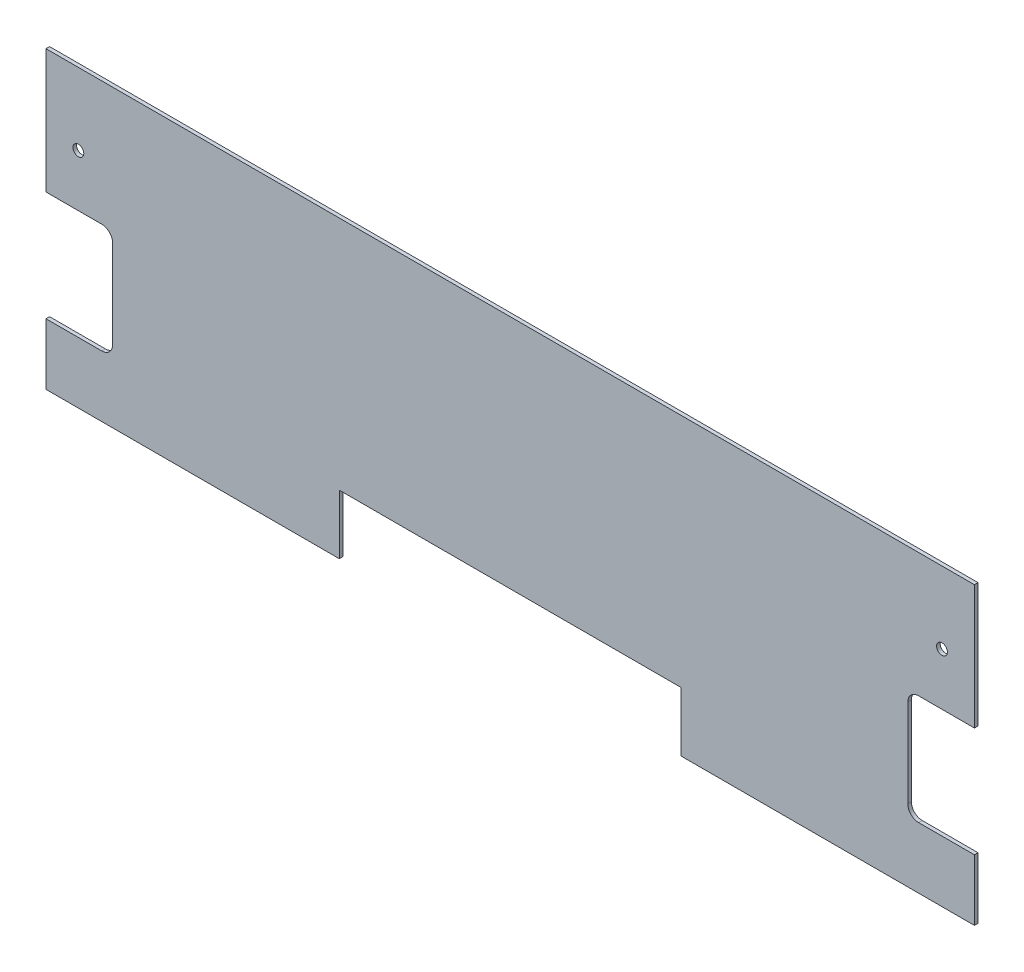
SolidWorks part; units mm, degrees
material "Film PE haute densité"
ref_plane "Front" through (0, 0, 0) normal (0, 0, 1) x (1, 0, 0)
ref_plane "Top" through (0, 0, 0) normal (0, 1, 0) x (1, 0, 0)
ref_plane "Right" through (0, 0, 0) normal (1, 0, 0) x (0, 0, -1)
sketch "Esquisse1" plane through (0, 0, 0) normal (0, 0, 1) x (1, 0, 0)
  line L0 (47.5, -82) -> (129, -82)
  line L1 (-129, -82) -> (-47.5, -82)
  line L2 (-129, -82) -> (-129, 0)
  line L3 (-129, 0) -> (129, 0)
  line L4 (129, -82) -> (129, 0)
  line L6 (-47.5, -82) -> (-47.5, -65.5)
  line L7 (-47.5, -65.5) -> (47.5, -65.5)
  line L8 (47.5, -82) -> (47.5, -65.5)
  dimension "D1" = 82
  dimension "D2" = 16.5
  dimension "D3" = 95
  dimension "D4" = 258
base flange "Tôle de base pliée1" sketch "Esquisse1" thickness 1 reverse thickness direction no parameters "D1"=1.5
sketch "Esquisse6" plane through (0, 0, 0) normal (0, 0, 1) x (1, 0, 0)
  line L0 (-129, 0) -> (-129, -82) construction
  line L1 (-129, -34.5) -> (-110.5, -34.5)
  line L2 (-129, -34.5) -> (-129, -65)
  line L3 (-129, -65) -> (-110.5, -65)
  line L4 (-110.5, -34.5) -> (-110.5, -65)
  line L5 (0, -50) -> (0, 50) construction
  line L6 (129, -65) -> (110.5, -65)
  line L7 (110.5, -34.5) -> (110.5, -65)
  line L8 (129, -34.5) -> (110.5, -34.5)
  line L9 (129, -34.5) -> (129, -65)
  line L10 (-129, -82) -> (-47.5, -82) construction
  line L11 (129, 0) -> (-129, 0) construction
  circle A0 centre (-120, -20) radius 1.5
  circle A1 centre (120, -20) radius 1.5
  dimension "D4" = 240
  dimension "D5" = 20
  dimension "D6" = 3
  dimension "D1" = 221
  dimension "D2" = 17
  dimension "D3" = 30.5
extrude "Enlèv. mat.-Extru.1" cut sketch "Esquisse6" against normal blind 1 normal cut yes
fillet "Congé1" radius 3 4 edges at (110.5, -34.5, -0.5) (110.5, -65, -0.5) (-110.5, -65, -0.5) (-110.5, -34.5, -0.5)
sketch "Lignes de pliage1" [suppressed] plane through (0, 0, 0) normal (0, 1, 0) x (1, 0, 0)
sketch "Cube de visualisation1" [suppressed] plane through (0, 0, 0) normal (0, 1, 0) x (1, 0, 0)
sheet metal parameters "Tôlerie1" thickness 1 parameters "D1"=1.5
flat pattern "Etat déplié1" [suppressed]
sketch "Lignes de pliage2" plane through (0, 0, 0) normal (0, 1, 0) x (1, 0, 0)
sketch3d "Cube de visualisation2" [suppressed]
  line L0 (-120, -82, 0) -> (120, -82, 0) construction
  line L1 (-120, 0, 0) -> (120, 0, 0) construction
  line L2 (-120, -82, 0) -> (-120, 0, 0) construction
  line L3 (120, -82, 0) -> (120, 0, 0) construction
sheet metal parameters "Tôlerie2" thickness 1 parameters "D1"=1.5
flat pattern "Etat déplié1"
sketch "Lignes de pliage2" plane through (0, 0, 0) normal (0, 1, 0) x (1, 0, 0)
sketch3d "Cube de visualisation2" [suppressed]
  line L0 (-129, -82, 0) -> (129, -82, 0) construction
  line L1 (-129, 0, 0) -> (129, 0, 0) construction
  line L2 (-129, -82, 0) -> (-129, 0, 0) construction
  line L3 (129, -82, 0) -> (129, 0, 0) construction
